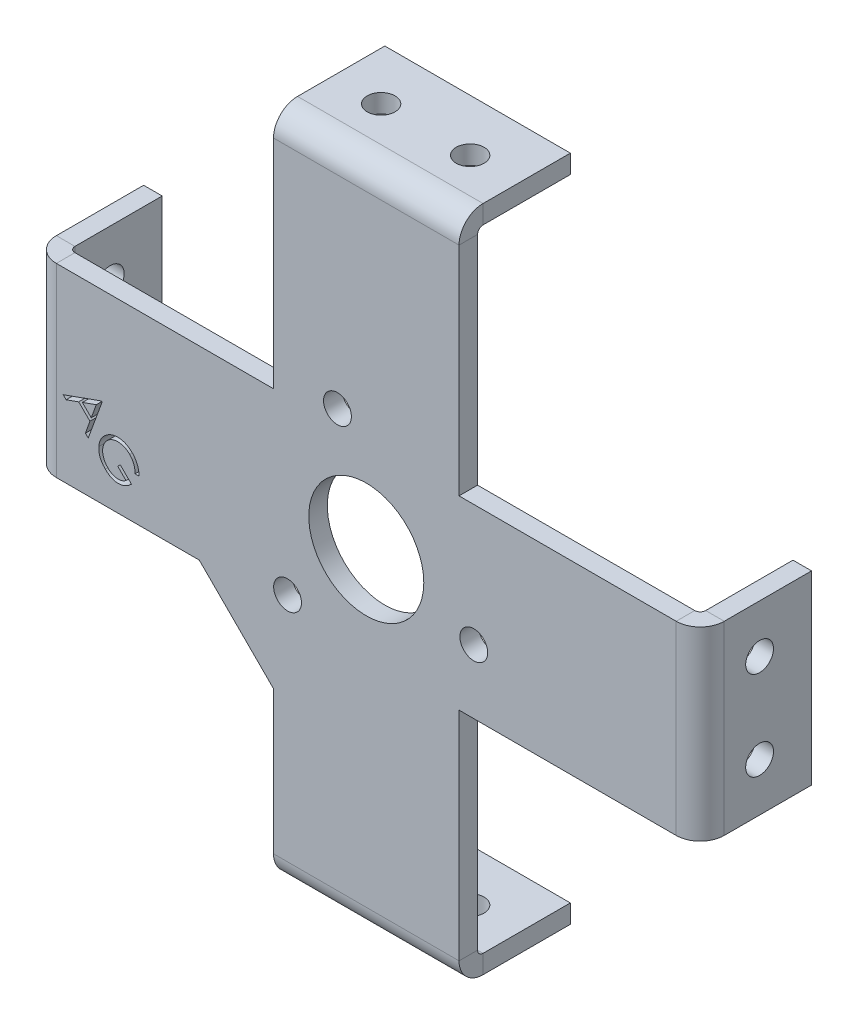
SolidWorks part; units mm, degrees
note: The reader was unsure of these and kept them because the rebuilt part matched: thickness of "Base-Flange1", "Edge-Flange1", "Edge-Flange2", "Edge-Flange3", "Edge-Flange4", "Sheet-Metal1", "Sheet-Metal2", "Sheet-Metal3", "Sheet-Metal4", "Sheet-Metal5", "Sheet-Metal6", "Sheet-Metal7"; flange length of "Edge-Flange1", "Edge-Flange2", "Edge-Flange3", "Edge-Flange4".
material "6061 Alloy"
ref_plane "Front Plane" through (0, 0, 0) normal (0, 0, 1) x (1, 0, 0)
ref_plane "Top Plane" through (0, 0, 0) normal (0, 1, 0) x (1, 0, 0)
ref_plane "Right Plane" through (0, 0, 0) normal (1, 0, 0) x (0, 0, -1)
sketch "Sketch1" plane through (0, 0, 0) normal (0, 0, 1) x (1, 0, 0)
  line L0 (-45, 12.5) -> (-12.5, 12.5)
  line L1 (-12.5, 45) -> (12.5, 45) construction
  line L2 (-12.5, 45) -> (-12.5, -45) construction
  line L3 (-12.5, -45) -> (12.5, -45) construction
  line L4 (12.5, 45) -> (12.5, -45) construction
  line L5 (-12.5, 45) -> (12.5, -45) construction
  line L6 (-12.5, -45) -> (12.5, 45) construction
  line L7 (-45, 12.5) -> (45, 12.5) construction
  line L8 (-45, 12.5) -> (-45, -12.5) construction
  line L9 (-45, -12.5) -> (45, -12.5) construction
  line L10 (45, 12.5) -> (45, -12.5) construction
  line L11 (-45, 12.5) -> (45, -12.5) construction
  line L12 (-45, -12.5) -> (45, 12.5) construction
  line L13 (-12.5, 12.5) -> (-12.5, 45)
  line L14 (-12.5, 45) -> (12.5, 45)
  line L15 (12.5, 45) -> (12.5, 12.5)
  line L16 (12.5, 12.5) -> (45, 12.5)
  line L17 (45, 12.5) -> (45, -12.5)
  line L18 (45, -12.5) -> (12.5, -12.5)
  line L19 (12.5, -12.5) -> (12.5, -45)
  line L20 (12.5, -45) -> (-12.5, -45)
  line L21 (-12.5, -45) -> (-12.5, -12.5)
  line L22 (-12.5, -12.5) -> (-45, -12.5)
  line L23 (-45, -12.5) -> (-45, 12.5)
  line L24 (14.4889, -3.8823) -> (-3.8823, 14.4889) construction
  line L25 (-3.8823, 14.4889) -> (-10.6066, -10.6066) construction
  line L26 (-10.6066, -10.6066) -> (14.4889, -3.8823) construction
  line L27 (0, 0) -> (14.4889, -3.8823) construction
  line L28 (-3.8823, 14.4889) -> (0, 0) construction
  line L29 (0, 0) -> (-10.6066, -10.6066) construction
  line L30 (0, 0) -> (0, -24.9108) construction
  circle A0 centre (0, 0) radius 7.75
  circle A1 centre (14.4889, -3.8823) radius 1.875
  circle A2 centre (-3.8823, 14.4889) radius 1.875
  circle A3 centre (-10.6066, -10.6066) radius 1.875
  point P0 (0, 0)
  point P5 (0, 0)
  dimension "D3" = 15.5
  dimension "D4" = 3.75
  dimension "D1" = 25
  dimension "D2" = 90
  dimension "D5" = 15
  dimension "D6" = 45
base flange "Base-Flange1" sketch "Sketch1" thickness 2.5 reverse thickness direction no parameters "D1"=0.7366
edge flange "Edge-Flange1" sketch "Sketch8" flange angle 90 flange length 15 flange position material inside bend radius 0.7366 thickness 2.5 relief rectangular parameters "D6"=10
sketch "Sketch8" plane through (-45, 0, -2.5) normal (-1, 0, 0) x (0, 1, 0)
  line L2 (-12.5, 0) -> (-12.5, 12.5)
  line L3 (-12.5, 12.5) -> (12.5, 12.5)
  line L4 (12.5, 12.5) -> (12.5, 0)
  line L11 (12.5, 0) -> (-12.5, 0) construction
  line L12 (12.5, 0) -> (-12.5, 0)
bend "EdgeBend1" bend radius 0.7366 bend angle 90 parameters "D5"=1
edge flange "Edge-Flange2" sketch "Sketch11" flange angle 90 flange length 15 flange position material inside bend radius 0.7366 thickness 2.5 relief rectangular parameters "D6"=10
sketch "Sketch11" plane through (0, 45, -2.5) normal (0, 1, 0) x (1, 0, 0)
  line L0 (12.5, 0) -> (-12.5, 0) construction
  line L1 (12.5, 0) -> (-12.5, 0)
  line L2 (-12.5, 0) -> (-12.5, 12.5)
  line L3 (-12.5, 12.5) -> (12.5, 12.5)
  line L4 (12.5, 12.5) -> (12.5, 0)
bend "EdgeBend2" bend radius 0.7366 bend angle 90 parameters "D5"=2
edge flange "Edge-Flange3" sketch "Sketch14" flange angle 90 flange length 15 flange position material inside bend radius 0.7366 thickness 2.5 relief rectangular parameters "D6"=10
sketch "Sketch14" plane through (45, 0, -2.5) normal (1, 0, 0) x (0, -1, 0)
  line L0 (12.5, 0) -> (-12.5, 0) construction
  line L1 (12.5, 0) -> (-12.5, 0)
  line L2 (-12.5, 0) -> (-12.5, 12.5)
  line L3 (-12.5, 12.5) -> (12.5, 12.5)
  line L4 (12.5, 12.5) -> (12.5, 0)
bend "EdgeBend3" bend radius 0.7366 bend angle 90 parameters "D5"=3
edge flange "Edge-Flange4" sketch "Sketch17" flange angle 90 flange length 15 flange position material inside bend radius 0.7366 thickness 2.5 relief rectangular parameters "D6"=10
sketch "Sketch17" plane through (0, -45, -2.5) normal (0, -1, 0) x (-1, 0, 0)
  line L0 (12.5, 0) -> (-12.5, 0) construction
  line L1 (12.5, 0) -> (-12.5, 0)
  line L2 (-12.5, 0) -> (-12.5, 12.5)
  line L3 (-12.5, 12.5) -> (12.5, 12.5)
  line L4 (12.5, 12.5) -> (12.5, 0)
bend "EdgeBend4" bend radius 0.7366 bend angle 90 parameters "D5"=4
sketch "Sketch18" plane through (0, -45, 0) normal (0, -1, 0) x (1, 0, 0)
  line L1 (12.5, -15) -> (12.5, -3.2366) construction
  circle A0 centre (6, -8) radius 1.875
  circle A1 centre (-6, -8) radius 1.875
  dimension "D1" = 3.75
  dimension "D3" = 12
  dimension "D2" = 8
  dimension "D4" = 6.5
extrude "Cut-Extrude1" cut sketch "Sketch18" against normal through all normal cut yes
pattern_circular "CirPattern1" count 2 every 90 about axis through (0, 0, -2.5) along (0, 0, 1) of "Cut-Extrude1"
chamfer "Chamfer1" distance 10 angle 45 1 edges at (-12.5, -12.5, -1.25)
sketch "Sketch19" plane through (0, 0, 0) normal (0, 0, 1) x (1, 0, 0)
  line L0 (-40.9543, -2.2481) -> (-28.6009, -14.6015) construction
  line L1 (-22.5, -12.5) -> (-12.5, -22.5) construction
  text T0 "AG" font "Century Gothic" height 5
extrude "Cut-Extrude2" cut sketch "Sketch19" against normal up to next normal cut yes
sketch "Bend-Lines1" [suppressed] plane through (0, 0, 0) normal (0, 1, 0) x (1, 0, 0)
sketch "Bounding-Box1" [suppressed] plane through (0, 0, 0) normal (0, 1, 0) x (1, 0, 0)
sheet metal parameters "Sheet-Metal1" thickness 2.5 parameters "D1"=0.7366
flat pattern "Flat-Pattern1" [suppressed]
sketch "Bend-Lines2" plane through (0, 0, 0) normal (0, 1, 0) x (1, 0, 0)
sketch3d "Bounding-Box2" [suppressed]
  line L0 (0, 57.5, 0) -> (-57.5, 0, 0) construction
  line L1 (57.5, 0, 0) -> (0, -57.5, 0) construction
  line L2 (0, 57.5, 0) -> (57.5, 0, 0) construction
  line L3 (-57.5, 0, 0) -> (0, -57.5, 0) construction
sheet metal parameters "Sheet-Metal2" thickness 2.5 parameters "D1"=0.7366
flat pattern "Flat-Pattern1"
sketch "Bend-Lines2" plane through (0, 0, 0) normal (0, 0, 1) x (1, 0, 0)
  line L0 (-44.3946, 12.5) -> (-44.3946, -12.5) construction
  line L1 (-44.3946, 12.5) -> (-44.3946, -12.5) construction
sketch3d "Bounding-Box2" [suppressed]
  line L0 (-6.8946, -64.3946, 0) -> (57.5, 0, 0) construction
  line L1 (-71.2892, 0, 0) -> (-6.8946, 64.3946, 0) construction
  line L2 (-6.8946, -64.3946, 0) -> (-71.2892, 0, 0) construction
  line L3 (57.5, 0, 0) -> (-6.8946, 64.3946, 0) construction
bend of the flat pattern "Flatten-<EdgeBend1>1"
sheet metal parameters "Sheet-Metal3" thickness 2.5 parameters "D1"=0.7366
flat pattern "Flat-Pattern1"
sketch "Bend-Lines2" plane through (0, 0, 0) normal (0, 0, 1) x (1, 0, 0)
  line L0 (-44.3946, 12.5) -> (-44.3946, -12.5) construction
  line L1 (-44.3946, 12.5) -> (-44.3946, -12.5) construction
  line L2 (12.5, 44.3946) -> (-12.5, 44.3946) construction
  line L3 (12.5, 44.3946) -> (-12.5, 44.3946) construction
sketch3d "Bounding-Box2" [suppressed]
  line L0 (-6.8946, -64.3946, 0) -> (64.3946, 6.8946, 0) construction
  line L1 (-71.2892, 0, 0) -> (0, 71.2892, 0) construction
  line L2 (-6.8946, -64.3946, 0) -> (-71.2892, 0, 0) construction
  line L3 (64.3946, 6.8946, 0) -> (0, 71.2892, 0) construction
bend of the flat pattern "Flatten-<EdgeBend1>1"
bend of the flat pattern "Flatten-<EdgeBend2>1"
sheet metal parameters "Sheet-Metal4" thickness 2.5 parameters "D1"=0.7366
flat pattern "Flat-Pattern1"
sketch "Bend-Lines2" plane through (0, 0, 0) normal (0, 0, 1) x (1, 0, 0)
  line L0 (-44.3946, 12.5) -> (-44.3946, -12.5) construction
  line L1 (-44.3946, 12.5) -> (-44.3946, -12.5) construction
  line L2 (12.5, 44.3946) -> (-12.5, 44.3946) construction
  line L3 (12.5, 44.3946) -> (-12.5, 44.3946) construction
  line L4 (44.3946, -12.5) -> (44.3946, 12.5) construction
  line L5 (44.3946, -12.5) -> (44.3946, 12.5) construction
sketch3d "Bounding-Box2" [suppressed]
  line L0 (0, 71.2892, 0) -> (71.2892, 0, 0) construction
  line L1 (-71.2892, 0, 0) -> (0, -71.2892, 0) construction
  line L2 (0, 71.2892, 0) -> (-71.2892, 0, 0) construction
  line L3 (71.2892, 0, 0) -> (0, -71.2892, 0) construction
bend of the flat pattern "Flatten-<EdgeBend1>1"
bend of the flat pattern "Flatten-<EdgeBend2>1"
bend of the flat pattern "Flatten-<EdgeBend3>1"
sheet metal parameters "Sheet-Metal5" thickness 2.5 parameters "D1"=0.7366
flat pattern "Flat-Pattern1"
sketch "Bend-Lines2" plane through (0, 0, 0) normal (0, 0, 1) x (1, 0, 0)
  line L0 (-44.3946, 12.5) -> (-44.3946, -12.5) construction
  line L1 (-44.3946, 12.5) -> (-44.3946, -12.5) construction
  line L2 (12.5, 44.3946) -> (-12.5, 44.3946) construction
  line L3 (12.5, 44.3946) -> (-12.5, 44.3946) construction
  line L4 (44.3946, -12.5) -> (44.3946, 12.5) construction
  line L5 (44.3946, -12.5) -> (44.3946, 12.5) construction
  line L6 (-12.5, -44.3946) -> (12.5, -44.3946) construction
  line L7 (-12.5, -44.3946) -> (12.5, -44.3946) construction
sketch3d "Bounding-Box2" [suppressed]
  line L0 (0, -71.2892, 0) -> (71.2892, 0, 0) construction
  line L1 (-71.2892, 0, 0) -> (0, 71.2892, 0) construction
  line L2 (0, -71.2892, 0) -> (-71.2892, 0, 0) construction
  line L3 (71.2892, 0, 0) -> (0, 71.2892, 0) construction
bend of the flat pattern "Flatten-<EdgeBend1>1"
bend of the flat pattern "Flatten-<EdgeBend2>1"
bend of the flat pattern "Flatten-<EdgeBend3>1"
bend of the flat pattern "Flatten-<EdgeBend4>1"
sheet metal parameters "Sheet-Metal6" thickness 2.5 parameters "D1"=0.7366
flat pattern "Flat-Pattern1"
sketch "Bend-Lines2" plane through (0, 0, 0) normal (0, 0, 1) x (1, 0, 0)
  line L0 (-44.3946, 12.5) -> (-44.3946, -12.5) construction
  line L1 (-44.3946, 12.5) -> (-44.3946, -12.5) construction
  line L2 (12.5, 44.3946) -> (-12.5, 44.3946) construction
  line L3 (12.5, 44.3946) -> (-12.5, 44.3946) construction
  line L4 (44.3946, -12.5) -> (44.3946, 12.5) construction
  line L5 (44.3946, -12.5) -> (44.3946, 12.5) construction
  line L6 (-12.5, -44.3946) -> (12.5, -44.3946) construction
  line L7 (-12.5, -44.3946) -> (12.5, -44.3946) construction
sketch3d "Bounding-Box2" [suppressed]
  line L0 (0, -71.2892, 0) -> (71.2892, 0, 0) construction
  line L1 (-71.2892, 0, 0) -> (0, 71.2892, 0) construction
  line L2 (0, -71.2892, 0) -> (-71.2892, 0, 0) construction
  line L3 (71.2892, 0, 0) -> (0, 71.2892, 0) construction
bend of the flat pattern "Flatten-<EdgeBend1>1"
bend of the flat pattern "Flatten-<EdgeBend2>1"
bend of the flat pattern "Flatten-<EdgeBend3>1"
bend of the flat pattern "Flatten-<EdgeBend4>1"
sheet metal parameters "Sheet-Metal7" thickness 2.5 parameters "D1"=0.7366
flat pattern "Flat-Pattern1"
sketch "Bend-Lines2" plane through (0, 0, 0) normal (0, 0, 1) x (1, 0, 0)
  line L0 (-44.3946, 12.5) -> (-44.3946, -12.5) construction
  line L1 (-44.3946, 12.5) -> (-44.3946, -12.5) construction
  line L2 (12.5, 44.3946) -> (-12.5, 44.3946) construction
  line L3 (12.5, 44.3946) -> (-12.5, 44.3946) construction
  line L4 (44.3946, -12.5) -> (44.3946, 12.5) construction
  line L5 (44.3946, -12.5) -> (44.3946, 12.5) construction
  line L6 (-12.5, -44.3946) -> (12.5, -44.3946) construction
  line L7 (-12.5, -44.3946) -> (12.5, -44.3946) construction
sketch3d "Bounding-Box2" [suppressed]
  line L0 (0, -71.2892, 0) -> (71.2892, 0, 0) construction
  line L1 (-71.2892, 0, 0) -> (0, 71.2892, 0) construction
  line L2 (0, -71.2892, 0) -> (-71.2892, 0, 0) construction
  line L3 (71.2892, 0, 0) -> (0, 71.2892, 0) construction
bend of the flat pattern "Flatten-<EdgeBend1>1"
bend of the flat pattern "Flatten-<EdgeBend2>1"
bend of the flat pattern "Flatten-<EdgeBend3>1"
bend of the flat pattern "Flatten-<EdgeBend4>1"
sheet metal parameters "Sheet-Metal8" thickness 0.7366 parameters "D1"=0.7366
flat pattern "Flat-Pattern8"
sketch "Bend-Lines3" plane through (0, 0, 0) normal (0, 0, 1) x (1, 0, 0)
  line L0 (-12.5, -43.3237) -> (12.5, -43.3237) construction
  line L1 (43.3237, -12.5) -> (43.3237, 12.5) construction
  line L2 (12.5, 43.3237) -> (-12.5, 43.3237) construction
  line L3 (-43.3237, 12.5) -> (-43.3237, -12.5) construction
  line L4 (-12.5, -43.3237) -> (12.5, -43.3237) construction
  line L5 (43.3237, -12.5) -> (43.3237, 12.5) construction
  line L6 (12.5, 43.3237) -> (-12.5, 43.3237) construction
  line L7 (-43.3237, 12.5) -> (-43.3237, -12.5) construction
sketch3d "Bounding-Box3" [suppressed]
  line L0 (0, 69.1473, 0) -> (69.1473, 0, 0) construction
  line L1 (-69.1473, 0, 0) -> (0, -69.1473, 0) construction
  line L2 (0, 69.1473, 0) -> (-69.1473, 0, 0) construction
  line L3 (69.1473, 0, 0) -> (0, -69.1473, 0) construction
bend of the flat pattern "Flatten-<EdgeBend4>2"
bend of the flat pattern "Flatten-<EdgeBend3>2"
bend of the flat pattern "Flatten-<EdgeBend2>2"
bend of the flat pattern "Flatten-<EdgeBend1>2"
sheet metal parameters "Sheet-Metal9" thickness 0.7366 parameters "D1"=0.7366
flat pattern "Flat-Pattern9"
sketch "Bend-Lines4" plane through (0, 0, 0) normal (0, 1, 0) x (1, 0, 0)
sketch3d "Bounding-Box4" [suppressed]
  line L0 (-37.7409, -3.4101, 0) -> (-35.8709, -2.7441, 0) construction
  line L1 (-38.254, -1.9696, 0) -> (-36.384, -1.3036, 0) construction
  line L2 (-37.7409, -3.4101, 0) -> (-38.254, -1.9696, 0) construction
  line L3 (-35.8709, -2.7441, 0) -> (-36.384, -1.3036, 0) construction
